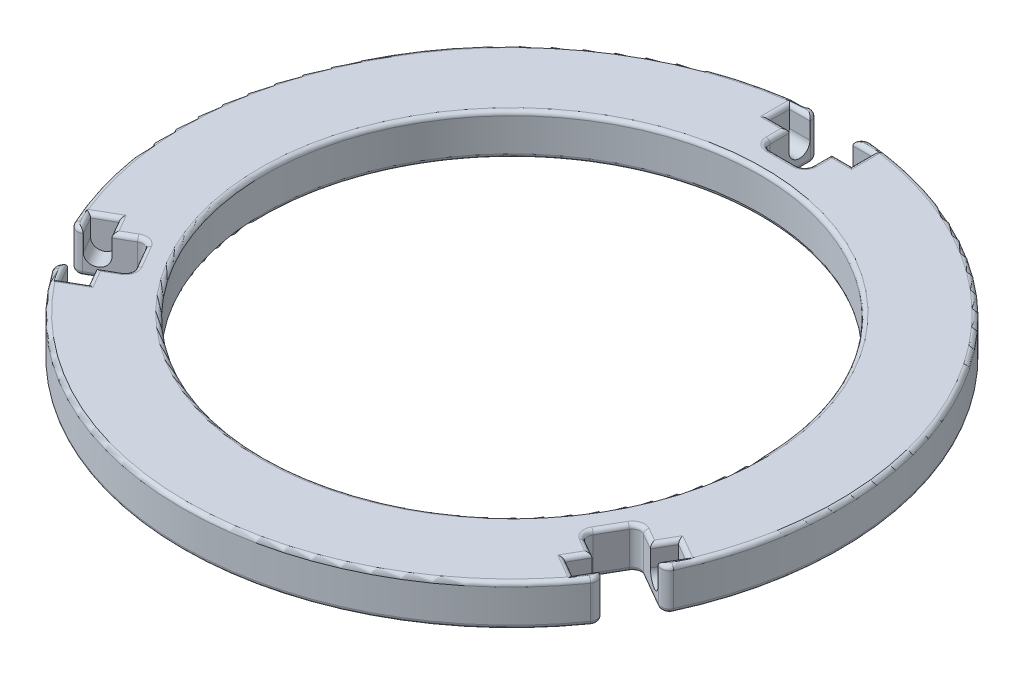
SolidWorks part; units mm, degrees
ref_plane "Front Plane" through (0, 0, 0) normal (0, 0, 1) x (1, 0, 0)
ref_plane "Top Plane" through (0, 0, 0) normal (0, 1, 0) x (1, 0, 0)
ref_plane "Right Plane" through (0, 0, 0) normal (1, 0, 0) x (0, 0, -1)
sketch "Sketch1" plane through (0, 0, 0) normal (0, 1, 0) x (1, 0, 0)
  line L0 (0, 0) -> (0, 121.6932) construction
  line L1 (0, 75) -> (-113.527, 75) construction
  line L2 (0, 65.8866) -> (-3.2, 65.8866)
  line L3 (-5.2, 67.8866) -> (-5.2, 77.667)
  line L4 (0, 65.8866) -> (3.2, 65.8866)
  line L5 (5.2, 67.8866) -> (5.2, 77.667)
  line L6 (61.3915, -29.4399) -> (69.8616, -34.3302)
  line L7 (57.0594, -32.9433) -> (58.6594, -30.172)
  line L8 (57.0594, -32.9433) -> (55.4594, -35.7146)
  line L9 (56.1915, -38.4466) -> (64.6616, -43.3368)
  line L10 (-56.1915, -38.4466) -> (-64.6616, -43.3368)
  line L11 (-57.0594, -32.9433) -> (-55.4594, -35.7146)
  line L12 (-57.0594, -32.9433) -> (-58.6594, -30.172)
  line L13 (-61.3915, -29.4399) -> (-69.8616, -34.3302)
  circle A0 centre (0, 0) radius 75 construction
  arc A1 (-7.3846, 79.6584) -> (-72.6785, -33.434) centre (0, 0) ccw
  circle A2 centre (0, 0) radius 60.125
  arc A3 (7.3846, 79.6584) -> (5.2, 77.667) centre (7.2, 77.667) ccw
  arc A4 (5.2, 67.8866) -> (3.2, 65.8866) centre (3.2, 67.8866) cw
  arc A5 (-3.2, 65.8866) -> (-5.2, 67.8866) centre (-3.2, 67.8866) cw
  arc A6 (-5.2, 77.667) -> (-7.3846, 79.6584) centre (-7.2, 77.667) ccw
  arc A7 (69.8616, -34.3302) -> (72.6785, -33.434) centre (70.8616, -32.5981) ccw
  arc A8 (58.6594, -30.172) -> (61.3915, -29.4399) centre (60.3915, -31.172) cw
  arc A9 (56.1915, -38.4466) -> (55.4594, -35.7146) centre (57.1915, -36.7146) cw
  arc A10 (65.2939, -46.2245) -> (64.6616, -43.3368) centre (63.6616, -45.0689) ccw
  arc A11 (-64.6616, -43.3368) -> (-65.2939, -46.2245) centre (-63.6616, -45.0689) ccw
  arc A12 (-55.4594, -35.7146) -> (-56.1915, -38.4466) centre (-57.1915, -36.7146) cw
  arc A13 (-61.3915, -29.4399) -> (-58.6594, -30.172) centre (-60.3915, -31.172) cw
  arc A14 (-72.6785, -33.434) -> (-69.8616, -34.3302) centre (-70.8616, -32.5981) ccw
  arc A15 (72.6785, -33.434) -> (7.3846, 79.6584) centre (0, 0) ccw
  arc A16 (-65.2939, -46.2245) -> (65.2939, -46.2245) centre (0, 0) ccw
  point P16 (5.2, 65.8866)
  point P19 (-5.2, 65.8866)
  point P51 (0, 0)
  dimension "D1" = 150
  dimension "D2" = 160
  dimension "D3" = 120.2501
  dimension "D6" = 2
  dimension "D4" = 5.2
  dimension "D5" = 5.2
  dimension "D7" = 3
extrude "Boss-Extrude1" add sketch "Sketch1" along normal blind 10
sketch "Sketch3" plane through (-5.2, 0, 0) normal (1, 0, 0) x (0, 0, -1)
  line L0 (0, 0) -> (75, 0) construction
  line L1 (75, 0) -> (75, 42.3431) construction
  line L2 (77.55, 10) -> (77.55, 5)
  line L3 (67.8866, 10) -> (77.667, 10) construction
  line L4 (77.55, 5) -> (72.45, 5) construction
  line L5 (72.45, 5) -> (72.45, 10)
  line L6 (72.45, 10) -> (77.55, 10)
  arc A0 (72.45, 5) -> (77.55, 5) centre (75, 5) ccw
  dimension "D1" = 75
  dimension "D2" = 2.55
  dimension "D3" = 2.55
  dimension "D4" = 2.55
  dimension "D5" = 5
  dimension "D6" = 5
extrude "Cut-Extrude2" cut sketch "Sketch3" against normal blind 5 and the other way blind 15.2
pattern_circular "CirPattern1" count 3 every 120 about axis through (0, 0, 0) along (0, 1, 0) of "Cut-Extrude2"
fillet "Fillet3" radius 1 68 edges at (0, 0, 60.125) (5.8526, 0, -79.145) (5.2, 0, -72.7768) (4.6142, 0, -66.4723) (0, 0, -65.8866) (-4.6142, 0, -66.4723) (-5.2, 0, -72.7768) (-5.8526, 0, -79.145) (-69.282, 0, -40) (-71.4679, 0, 34.504) (-65.6265, 0, 31.8851) (-59.8738, 0, 29.2401) (-57.0594, 0, 32.9433) (-55.2596, 0, 37.2322) (-60.4265, 0, 40.8917) (-65.6153, 0, 44.641) (0, 0, 80) (65.6153, 0, 44.641) (60.4265, 0, 40.8917) (55.2596, 0, 37.2322) (57.0594, 0, 32.9433) (59.8738, 0, 29.2401) (65.6265, 0, 31.8851) (71.4679, 0, 34.504) (69.282, 0, -40) (-63.3103, 10, 45.4434) (-70.9603, 10, 32.1932) (-71.4679, 10, 34.504) (-69.282, 10, -40) (-5.8526, 10, -79.145) (-7.7, 10, -77.55) (-10.2, 10, -75) (-7.7, 10, -72.45) (-5.2, 10, -70.1683) (-4.6142, 10, -66.4723) (0, 10, -65.8866) (4.6142, 10, -66.4723) (5.2, 10, -70.1683) (7.6, 10, -72.45) (10, 10, -75) (7.6, 10, -77.55) (5.8526, 10, -79.145) (69.282, 10, -40) (71.4679, 10, 34.504) (63.3603, 10, 45.3568) (71.0103, 10, 32.1066) (70.0519, 10, 28.6665) (58.9435, 10, 42.8068) (66.5935, 10, 29.5566) (63.3675, 10, 30.5808) (59.8738, 10, 29.2401) (57.0594, 10, 32.9433) (55.2596, 10, 37.2322) (58.1675, 10, 39.5875) (59.9519, 10, 46.1603) (65.6153, 10, 44.641) (0, 10, 80) (-65.6153, 10, 44.641) (-59.8519, 10, 46.3335) (-66.5435, 10, 29.6432) (-58.8935, 10, 42.8934) (-58.1675, 10, 39.5875) (-55.2596, 10, 37.2322) (-57.0594, 10, 32.9433) (-59.8738, 10, 29.2401) (-63.3675, 10, 30.5808) (-69.9519, 10, 28.8397) (0, 10, 60.125)
